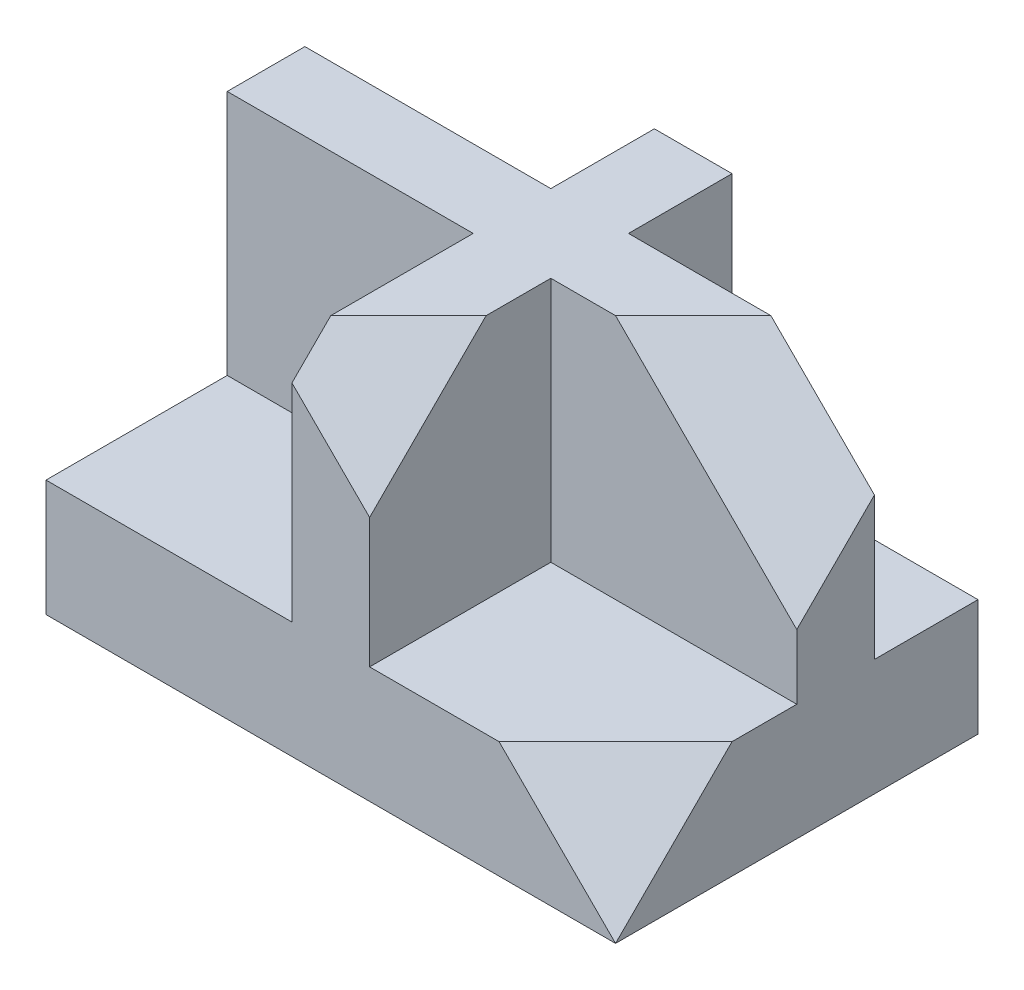
SolidWorks part; units mm, degrees
ref_plane "Front Plane" through (0, 0, 0) normal (0, 0, 1) x (1, 0, 0)
ref_plane "Top Plane" through (0, 0, 0) normal (0, 1, 0) x (1, 0, 0)
ref_plane "Right Plane" through (0, 0, 0) normal (1, 0, 0) x (0, 0, -1)
sketch "Sketch1" plane through (0, 0, 0) normal (0, 1, 0) x (1, 0, 0)
  line L0 (-42.24, 0) -> (-42.24, 56)
  line L1 (-42.24, 56) -> (45.76, 56)
  line L2 (45.76, 56) -> (45.76, 0)
  line L3 (45.76, 0) -> (-42.24, 0)
  line L4 (-4.24, 56) -> (-4.24, 0)
  line L5 (7.76, 56) -> (7.76, 0)
  line L6 (7.76, 0) -> (-4.24, 0)
  line L7 (-4.24, 56) -> (7.76, 56)
  line L8 (-42.24, 28) -> (-42.24, 40)
  line L9 (-42.24, 40) -> (45.76, 40)
  line L10 (45.76, 40) -> (45.76, 28)
  line L11 (45.76, 28) -> (-42.24, 28)
  dimension "D1" = 88
  dimension "D2" = 12
  dimension "D3" = 12
  dimension "D4" = 38
  dimension "D5" = 28
extrude "Boss-Extrude1" add sketch "Sketch1" along normal blind 18 contours L3 L0 L1 L2
extrude "Boss-Extrude2" add sketch "Sketch1<3>" along normal blind 56 contours L11 L4 L9 L0 | L11 L5 L9 L4 | L4 L9 L5 L1 | L5 L11 L4 L3 | L11 L2 L9 L5 region at (-23.24, 0, -34) region at (1.76, 0, -14) region at (1.76, 0, -34) region at (1.76, 0, -48) region at (26.76, 0, -34)
sketch "Sketch1<3>" plane through (0, 0, 0) normal (0, 1, 0) x (1, 0, 0) same geometry as "Sketch1"
sketch "Sketch2" plane through (45.76, 0, 0) normal (1, 0, 0) x (0, 0, -1)
  line L0 (56, 56) -> (56, 18) construction
  line L1 (56, 56) -> (56, 18)
  line L8 (56, 18) -> (40, 18)
  line L9 (40, 18) -> (40, 56)
  line L10 (40, 56) -> (28, 56)
  line L11 (28, 56) -> (28, 18)
  line L12 (28, 18) -> (0, 18)
  line L13 (0, 18) -> (0, 0)
  line L14 (0, 0) -> (56, 0)
  line L15 (56, 0) -> (56, 18)
  line L16 (56, 18) -> (40, 18)
  line L17 (40, 18) -> (40, 56)
  line L18 (40, 56) -> (28, 56)
  line L19 (28, 56) -> (28, 18)
  line L20 (28, 18) -> (0, 18)
  line L21 (0, 18) -> (0, 0)
  line L22 (0, 0) -> (56, 0)
  line L23 (56, 0) -> (56, 18)
  dimension "D1" = 0
sketch "Sketch3" plane through (0, 0, 0) normal (0, 0, 1) x (1, 0, 0)
  line L0 (45.76, 0) -> (-10.24, 56)
  line L1 (45.76, 0) -> (-42.24, 0) construction
  dimension "D1" = 45
ref_plane "Plane1" through (15.2533, 15.2533, 15.2533) normal (0.5774, 0.5774, 0.5774) x (0.4082, 0.4082, -0.8165)
sketch "Sketch4" plane through (15.2533, 15.2533, 15.2533) normal (0.5774, 0.5774, 0.5774) x (0.4082, 0.4082, -0.8165)
  line L1 (-47.2679, 71.5281) -> (114.0247, 71.5281)
  line L2 (-47.2679, 71.5281) -> (-47.2679, -57.0466)
  line L3 (-47.2679, -57.0466) -> (114.0247, -57.0466)
  line L4 (114.0247, 71.5281) -> (114.0247, -57.0466)
  line L5 (-47.2679, 71.5281) -> (114.0247, -57.0466) construction
  line L6 (-47.2679, -57.0466) -> (114.0247, 71.5281) construction
  point P0 (33.3784, 7.2408)
extrude "Cut-Extrude1" cut sketch "Sketch4" along normal blind 56
